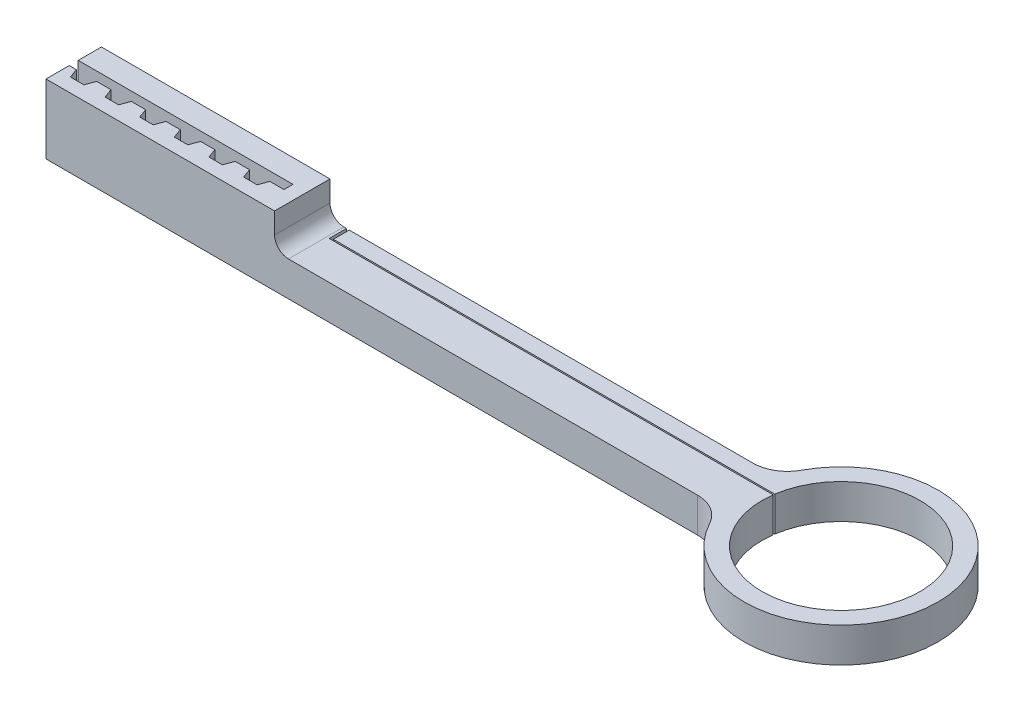
SolidWorks part; units mm, degrees
ref_plane "Спереди" through (0, 0, 0) normal (0, 0, 1) x (1, 0, 0)
ref_plane "Сверху" through (0, 0, 0) normal (0, 1, 0) x (1, 0, 0)
ref_plane "Справа" through (0, 0, 0) normal (1, 0, 0) x (0, 0, -1)
sketch "Эскиз1" plane through (0, 0, 0) normal (0, 1, 0) x (1, 0, 0)
  circle A0 centre (0, 0) radius 11.4
  circle A1 centre (0, 0) radius 14
  dimension "D1" = 22.8
  dimension "D2" = 28
extrude "ring" add sketch "Эскиз1" along normal blind 5
sketch "Эскиз2" plane through (0, 0, 0) normal (0, 1, 0) x (1, 0, 0)
  line L0 (34.0214, 0) -> (-42.1067, 0) construction
  line L1 (-10.7819, 4) -> (-10.7819, -4) construction
  line L2 (-10.7819, 4) -> (-110.7819, 4)
  line L4 (-10.7819, -4) -> (-110.7819, -4)
  line L5 (-110.7819, 4) -> (-110.7819, -4)
  circle A0 centre (0, 0) radius 11.5 construction
  arc A1 (-10.7819, 4) -> (-10.7819, -4) centre (0, 0) ccw
  point P9 (-10.7819, 0)
  dimension "D3" = 23
  dimension "D2" = 8
  dimension "D4" = 100
extrude "stick" add sketch "Эскиз2" along normal blind 5
sketch "Эскиз3" plane through (0, 0, 0) normal (0, 1, 0) x (1, 0, 0)
  line L0 (-110.7819, -4) -> (-13.4164, -4) construction
  line L1 (-110.7819, 4) -> (-77.7819, 4)
  line L2 (-110.7819, 4) -> (-110.7819, -4)
  line L3 (-110.7819, -4) -> (-77.7819, -4)
  line L4 (-77.7819, 4) -> (-77.7819, -4)
  dimension "D1" = 33
extrude "key" add sketch "Эскиз3" along normal blind 10
fillet "Скругление1" radius 5 2 edges at (-13.4164, 2.5, 4) (-13.4164, 2.5, -4)
ref_plane "Плоскость1" through (0, 2.5, 0) normal (0, 1, 0) x (-1, 0, 0)
sketch "Эскиз4" plane through (0, 2.5, 0) normal (0, 1, 0) x (1, 0, 0)
  line L0 (-110.7819, 0) -> (-77.7819, 0) construction
  line L1 (-110.7819, 4) -> (-110.7819, -4) construction
  line L2 (-77.7819, -4) -> (-77.7819, 4) construction
  line L3 (-110.7819, 0.65) -> (-80.2819, 0.65)
  line L4 (-109.2569, -2) -> (-107.3069, -2)
  line L5 (-109.5437, -0.65) -> (-90.7013, -0.65) construction
  line L6 (-109.7483, -0.65) -> (-109.2569, -2) construction
  line L7 (-109.7483, -0.65) -> (-109.2569, -2)
  line L8 (-107.3069, -2) -> (-106.8156, -0.65)
  line L9 (-108.2819, 0.7157) -> (-108.2819, -3.7603) construction
  line L10 (-109.7483, -0.65) -> (-110.7819, -0.65)
  line L11 (-106.8156, -0.65) -> (-105.7819, -0.65)
  line L12 (-110.7819, 0.65) -> (-110.7819, -0.65)
  line L13 (-104.7483, -0.65) -> (-105.7819, -0.65)
  line L14 (-104.2569, -2) -> (-102.3069, -2)
  line L15 (-102.3069, -2) -> (-101.8156, -0.65)
  line L16 (-101.8156, -0.65) -> (-100.7819, -0.65)
  line L17 (-104.7483, -0.65) -> (-104.2569, -2)
  line L18 (-99.7483, -0.65) -> (-100.7819, -0.65)
  line L19 (-99.2569, -2) -> (-97.3069, -2)
  line L20 (-97.3069, -2) -> (-96.8156, -0.65)
  line L21 (-96.8156, -0.65) -> (-95.7819, -0.65)
  line L22 (-99.7483, -0.65) -> (-99.2569, -2)
  line L24 (-94.7483, -0.65) -> (-95.7819, -0.65)
  line L25 (-94.2569, -2) -> (-92.3069, -2)
  line L26 (-92.3069, -2) -> (-91.8156, -0.65)
  line L27 (-91.8156, -0.65) -> (-90.7819, -0.65)
  line L28 (-94.7483, -0.65) -> (-94.2569, -2)
  line L43 (-89.7483, -0.65) -> (-90.7819, -0.65)
  line L44 (-89.2569, -2) -> (-87.3069, -2)
  line L45 (-87.3069, -2) -> (-86.8156, -0.65)
  line L46 (-86.8156, -0.65) -> (-85.7819, -0.65)
  line L47 (-89.7483, -0.65) -> (-89.2569, -2)
  line L48 (-84.7483, -0.65) -> (-85.7819, -0.65)
  line L49 (-84.2569, -2) -> (-82.3069, -2)
  line L50 (-82.3069, -2) -> (-81.8156, -0.65)
  line L51 (-81.8156, -0.65) -> (-80.7819, -0.65)
  line L52 (-84.7483, -0.65) -> (-84.2569, -2)
  line L53 (-80.7819, -0.65) -> (-80.2819, -0.65)
  line L54 (-80.2819, 0.65) -> (-80.2819, -0.65)
  point P12 (-108.2819, -2)
  dimension "D1" = 1.95
  dimension "D2" = 0.65
  dimension "D3" = 0.65
  dimension "D4" = 1.35
  dimension "D5" = 110
  dimension "D6" = 5
  dimension "D7" = 40
  dimension "D8" = 0.5
fillet "Скругление5" radius 2 1 edges at (-77.7819, 5, 0)
extrude "key hole" cut sketch "Эскиз4" against normal through all and the other way through all
sketch "Эскиз5" plane through (0, 0, 0) normal (0, -1, 0) x (1, 0, 0)
  line L0 (0, 0) -> (-70.3859, 0) construction
  line L1 (-75.4, -4) -> (-75.4, -1.5)
  line L3 (-75.4, -1.5) -> (0, -1.5)
  line L4 (0, -1.5) -> (0, -1.7)
  line L5 (0, -1.7) -> (-75, -1.7)
  line L6 (-75, -1.7) -> (-75, -4)
  line L7 (-75, -4) -> (-75.4, -4)
  line L8 (-16.7332, -4) -> (-110.7819, -4) construction
  dimension "D1" = 0.2
  dimension "D2" = 0.4
  dimension "D3" = 75
  dimension "D4" = 1.5
extrude "correction hole 1" cut sketch "Эскиз5" against normal through all
sketch "Эскиз6" plane through (0, 10, 0) normal (0, 1, 0) x (1, 0, 0)
  line L1 (-80.2819, 0.65) -> (-79.7819, 0.65)
  line L2 (-80.2819, 0.65) -> (-80.2819, -0.65)
  line L3 (-80.2819, -0.65) -> (-79.7819, -0.65)
  line L4 (-79.7819, 0.65) -> (-79.7819, -0.65)
  dimension "D1" = 0.5
extrude "correction hole" cut sketch "Эскиз6" against normal through all
